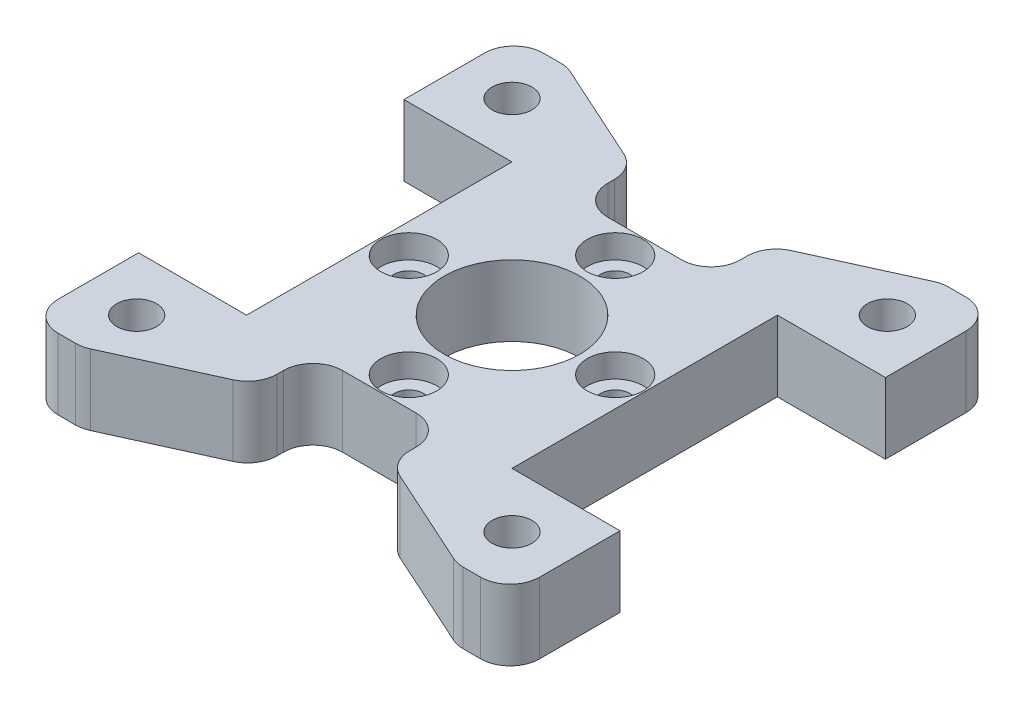
SolidWorks part; units mm, degrees
ref_plane "Front Plane" through (0, 0, 0) normal (0, 0, 1) x (1, 0, 0)
ref_plane "Top Plane" through (0, 0, 0) normal (0, 1, 0) x (1, 0, 0)
ref_plane "Right Plane" through (0, 0, 0) normal (1, 0, 0) x (0, 0, -1)
sketch "Sketch1" plane through (0, 0, 0) normal (0, 1, 0) x (1, 0, 0)
  line L0 (-31.8198, 31.8198) -> (0, 0) construction
  line L1 (-22.5, -22.5) -> (22.5, -22.5)
  line L2 (-22.5, -22.5) -> (-22.5, 22.5)
  line L3 (-22.5, 22.5) -> (22.5, 22.5)
  line L4 (22.5, -22.5) -> (22.5, 22.5)
  line L5 (-22.5, -22.5) -> (22.5, 22.5) construction
  line L6 (-22.5, 22.5) -> (22.5, -22.5) construction
  line L15 (0, 22.5) -> (0, -22.5) construction
  line L16 (0, 0) -> (31.8198, -31.8198) construction
  line L17 (-22.5, 0) -> (22.5, 0) construction
  line L18 (11.25, 22.5) -> (40.8198, 22.5)
  line L19 (11.25, 22.5) -> (11.25, 31.8198)
  line L20 (31.7885, 41.1398) -> (40.8198, 41.1398)
  line L21 (40.8198, 22.5) -> (40.8198, 41.1398)
  line L22 (0, 22.5) -> (22.5, 22.5) construction
  line L23 (11.25, 31.8198) -> (31.7885, 41.1398)
  line L24 (-40.8198, 22.5) -> (-40.8198, 41.1398)
  line L25 (-31.7885, 41.1398) -> (-40.8198, 41.1398)
  line L26 (-11.25, 31.8198) -> (-31.7885, 41.1398)
  line L27 (-11.25, 22.5) -> (-11.25, 31.8198)
  line L28 (-11.25, 22.5) -> (-40.8198, 22.5)
  line L29 (11.25, -22.5) -> (40.8198, -22.5)
  line L30 (40.8198, -22.5) -> (40.8198, -41.1398)
  line L31 (31.7885, -41.1398) -> (40.8198, -41.1398)
  line L32 (11.25, -31.8198) -> (31.7885, -41.1398)
  line L33 (11.25, -22.5) -> (11.25, -31.8198)
  line L34 (-11.25, -22.5) -> (-11.25, -31.8198)
  line L35 (-11.25, -22.5) -> (-40.8198, -22.5)
  line L36 (-40.8198, -22.5) -> (-40.8198, -41.1398)
  line L37 (-31.7885, -41.1398) -> (-40.8198, -41.1398)
  line L38 (-11.25, -31.8198) -> (-31.7885, -41.1398)
  point P0 (0, 0)
  point P6 (-31.8198, 31.8198)
  point P14 (31.8198, 31.8198)
  point P15 (31.8198, -31.8198)
  point P16 (-31.8198, -31.8198)
  point P17 (12.25, 32.4537)
  point P23 (37.0337, 41.1398)
  point P24 (12.25, 31.8198)
  point P25 (0, 0)
  dimension "D1" = 45
  dimension "D2" = 45
  dimension "D3" = 45
  dimension "D4" = 45
  dimension "D6" = 9.32
  dimension "D7" = 9
  dimension "D8" = 8.5
  dimension "D5" = 4
extrude "Boss-Extrude1" add sketch "Sketch1" along normal blind 12 contours L38 L34 L1 L35 L36 L37 | L1 L4 L3 L2 | L1 L33 L32 L31 L30 L29 | L23 L19 L3 L18 L21 L20 | L28 L3 L27 L26 L25 L24 region at (0, 0, 0) region at (-27.7031, 0, 30.5143) region at (-27.7031, 0, -30.5143) region at (27.7031, 0, 30.5143) region at (27.7031, 0, -30.5143)
sketch "Sketch2" plane through (0, 12, 0) normal (0, 1, 0) x (1, 0, 0)
  line L0 (0, 0) -> (-31.8198, 31.8198) construction
  line L1 (0, 22.5) -> (0, -22.5) construction
  line L2 (-11.25, 22.5) -> (11.25, 22.5) construction
  line L3 (-11.25, -22.5) -> (11.25, -22.5) construction
  line L4 (0, 0) -> (31.8198, -31.8198) construction
  line L5 (-22.5, 0) -> (22.5, 0) construction
  line L6 (-22.5, -22.5) -> (-22.5, 22.5) construction
  line L7 (22.5, -22.5) -> (22.5, 22.5) construction
  circle A0 centre (0, 0) radius 11.5
  circle A1 centre (-31.8198, 31.8198) radius 3.375
  circle A2 centre (31.8198, 31.8198) radius 3.375
  circle A3 centre (31.8198, -31.8198) radius 3.375
  circle A4 centre (-31.8198, -31.8198) radius 3.375
  circle A5 centre (0, 17.5) radius 2.5
  circle A6 centre (17.5, 0) radius 2.5
  circle A7 centre (0, -17.5) radius 2.5
  circle A8 centre (-17.5, 0) radius 2.5
  point P13 (13.1797, 4.3203)
  dimension "D1" = 23
  dimension "D2" = 6.75
  dimension "D6" = 5
  dimension "D3" = 45
  dimension "D4" = 45
  dimension "D7" = 5
  dimension "D5" = 4
  dimension "D8" = 4
extrude "Cut-Extrude1" cut sketch "Sketch2" against normal through all
sketch "Sketch3" plane through (0, 0, 0) normal (0, -1, 0) x (1, 0, 0)
  line L0 (31.8198, -31.8198) -> (0, 0) construction
  line L1 (0, 0) -> (-31.8198, 31.8198) construction
  circle A0 centre (31.8198, -31.8198) radius 7.5
  circle A1 centre (-31.8198, -31.8198) radius 7.5
  circle A2 centre (-31.8198, 31.8198) radius 7.5
  circle A3 centre (31.8198, 31.8198) radius 7.5
  dimension "D1" = 15
  dimension "D2" = 4
extrude "Cut-Extrude2" cut sketch "Sketch3" against normal blind 4.33
fillet "Fillet3" radius 5 16 edges at (-40.8198, 6, 41.1398) (-31.7885, 6, 41.1398) (-11.25, 6, 31.8198) (11.25, 6, 22.5) (-11.25, 6, 22.5) (40.8198, 6, 41.1398) (31.7885, 6, 41.1398) (11.25, 6, 31.8198) (-40.8198, 6, -41.1398) (-31.7885, 6, -41.1398) (-11.25, 6, -31.8198) (-11.25, 6, -22.5) (11.25, 6, -22.5) (11.25, 6, -31.8198) (31.7885, 6, -41.1398) (40.8198, 6, -41.1398)
sketch "Sketch4" plane through (0, 12, 0) normal (0, 1, 0) x (1, 0, 0)
  circle A0 centre (0, 17.5) radius 4.75
  circle A1 centre (17.5, 0) radius 4.75
  circle A2 centre (0, -17.5) radius 4.75
  circle A3 centre (-17.5, 0) radius 4.75
  circle A4 centre (17.5, 0) radius 2.5 construction
  point P3 (0, 0)
  dimension "D1" = 9.5
  dimension "D2" = 4
extrude "Cut-Extrude3" cut sketch "Sketch4" against normal blind 4
